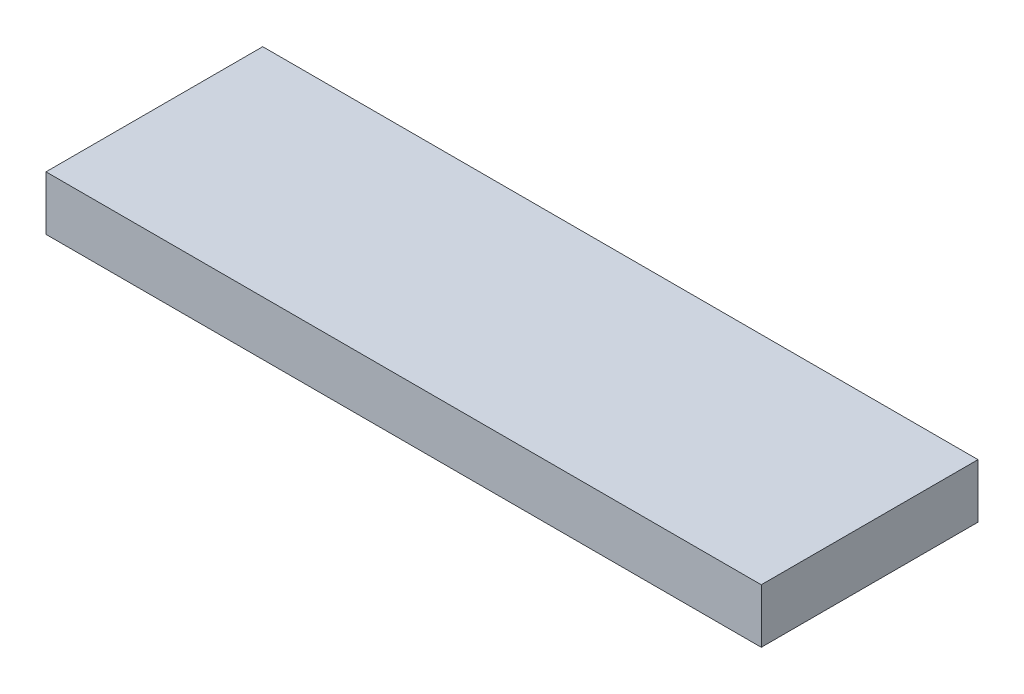
SolidWorks part; units mm, degrees
ref_plane "Front Plane" through (0, 0, 0) normal (0, 0, 1) x (1, 0, 0)
ref_plane "Top Plane" through (0, 0, 0) normal (0, 1, 0) x (1, 0, 0)
ref_plane "Right Plane" through (0, 0, 0) normal (1, 0, 0) x (0, 0, -1)
sketch "Sketch1" plane through (0, 0, 0) normal (0, 1, 0) x (1, 0, 0)
  line L1 (41.91, -12.7) -> (-41.91, -12.7)
  line L2 (41.91, -12.7) -> (41.91, 12.7)
  line L3 (41.91, 12.7) -> (-41.91, 12.7)
  line L4 (-41.91, -12.7) -> (-41.91, 12.7)
  line L5 (41.91, -12.7) -> (-41.91, 12.7) construction
  line L6 (41.91, 12.7) -> (-41.91, -12.7) construction
  point P0 (0, 0)
  dimension "D1" = 83.82
  dimension "D2" = 25.4
extrude "Box" add sketch "Sketch1" along normal blind 6.35
sketch "Sketch6" plane through (0, 6.35, 0) normal (0, 1, 0) x (1, 0, 0)
  line L0 (-17.4852, 0) -> (-25.1052, 0) construction
  line L1 (-17.4852, -5.08) -> (-25.1052, -5.08)
  line L2 (-17.4852, 5.08) -> (-25.1052, 5.08)
  line L3 (0, 0) -> (0, 12.7)
  line L4 (41.91, 12.7) -> (-41.91, 12.7) construction
  line L5 (0, 12.7) -> (0, -12.7)
  line L6 (-41.91, -12.7) -> (41.91, -12.7) construction
  arc A0 (-17.4852, -5.08) -> (-17.4852, 5.08) centre (-17.4852, 0) ccw
  arc A1 (-25.1052, 5.08) -> (-25.1052, -5.08) centre (-25.1052, 0) ccw
  point P2 (-21.2952, 0)
  point P12 (0, 0)
  point P16 (0, 0)
